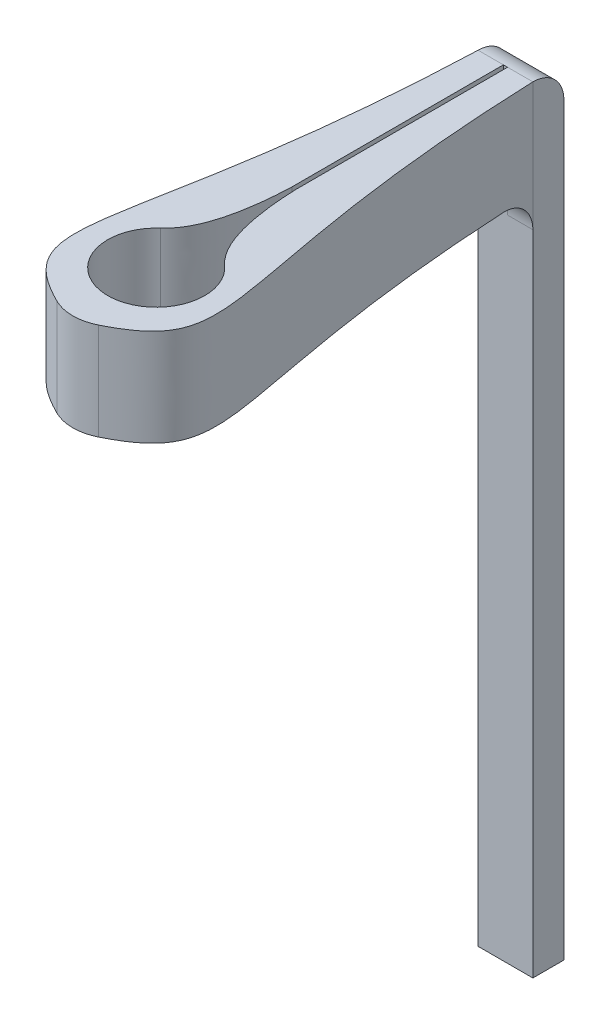
SolidWorks part; units mm, degrees
ref_plane "Front Plane" through (0, 0, 0) normal (0, 0, 1) x (1, 0, 0)
ref_plane "Top Plane" through (0, 0, 0) normal (0, 1, 0) x (1, 0, 0)
ref_plane "Right Plane" through (0, 0, 0) normal (1, 0, 0) x (0, 0, -1)
sketch "Sketch1" plane through (0, 0, 0) normal (0, 1, 0) x (1, 0, 0)
  line L0 (0, 0) -> (0, 6.2146) construction
  line L1 (-1.0541, 2.8957) -> (-0.1615, 3.6883) construction
  line L2 (-0.0683, 13.1387) -> (0.0683, 13.1387)
  line L3 (-0.0683, 13.1387) -> (-0.0683, 6.2146)
  line L5 (0.0683, 13.1387) -> (0.0683, 6.2146)
  line L6 (-0.1615, 3.6883) -> (-0.0683, 6.2146) construction
  line L9 (1.0541, 2.8957) -> (0.1615, 3.6883) construction
  line L10 (0.1615, 3.6883) -> (0.0683, 6.2146) construction
  line L11 (-0.8958, 13.1387) -> (-1.2101, 4.5709) construction
  line L12 (-1.2101, 4.5709) -> (-2.7776, 1.0836) construction
  line L20 (-2.7776, 1.0836) -> (-3.2771, 0.2019) construction
  line L21 (-3.2771, 0.2019) -> (0, -1.17) construction
  line L22 (0.8958, 13.1387) -> (1.2101, 4.5709) construction
  line L23 (1.2101, 4.5709) -> (2.7776, 1.0836) construction
  line L25 (2.7776, 1.0836) -> (3.2771, 0.2019) construction
  line L26 (3.2771, 0.2019) -> (0, -1.17) construction
  line L27 (-0.8958, 13.1387) -> (0, 13.1387)
  line L28 (0.8958, 13.1387) -> (0, 13.1387)
  arc A0 (-1.0541, 2.8957) -> (1.0541, 2.8957) centre (0, 1.7087) ccw
  spline S3 degree 2 poles (1.0541, 2.8957) (0.1615, 3.6883) (0.0683, 6.2146) knots 0 0 0 1 1 1
  spline S4 degree 2 poles (-1.0541, 2.8957) (-0.1615, 3.6883) (-0.0683, 6.2146) knots 0 0 0 1 1 1
  spline S5 degree 4 poles (-0.8958, 13.1387) (-1.2101, 4.5709) (-2.7776, 1.0836) (-3.2771, 0.2019) (0, -1.17) knots 0 0 0 0 0 1 1 1 1 1
  spline S6 degree 4 poles (0.8958, 13.1387) (1.2101, 4.5709) (2.7776, 1.0836) (3.2771, 0.2019) (0, -1.17) knots 0 0 0 0 0 1 1 1 1 1
  point P8 (-0.508, -2.5134)
  point P18 (0.508, -2.5134)
  point P21 (0, -2.54)
  dimension "D6" = 3.6883
  dimension "D1" = 3.175
  dimension "D3" = 0.8958
  dimension "D2" = 11.43
  dimension "D5" = 3.3189
  dimension "D7" = 4.5709
  dimension "D4" = 6.2146
extrude "Boss-Extrude1" add sketch "Sketch1" along normal blind 1.5875 and the other way blind 1.5875 contours S6 L28 L5 S3 A0 S4 L3 L27 S5 region at (0.082, 0, -9.6767)
ref_axis "Axis1" through (0, 0, -2.032) along (0, 0, 1)
ref_plane "Plane1" through (0, 0, 2.54) normal (0, 0, 1) x (1, 0, 0)
ref_axis "Axis2" through (0, 1.7463, 2.54) along (0, -1, 0)
fillet "Fillet1" radius 1.524 1 edges at (0, 0, 1.17)
ref_plane "Plane2" through (0, 0, -2.8957) normal (0, 0, -1) x (-1, 0, 0)
ref_plane "Plane3" through (0, 0, -3.4037) normal (0, 0, -1) x (-1, 0, 0)
sketch "Sketch2" plane through (0, 0, 0) normal (1, 0, 0) x (0, 0, -1)
  line L0 (13.1387, -1.5875) -> (13.1387, 1.5875) construction
  line L1 (13.1387, -1.5875) -> (13.1387, 1.5875)
  line L3 (13.1387, 1.5875) -> (14.1547, 1.5875)
  line L4 (13.1387, 1.5875) -> (13.1387, -23.8125)
  line L5 (13.1387, -23.8125) -> (14.1547, -23.8125)
  line L6 (14.1547, 1.5875) -> (14.1547, -23.8125)
  dimension "D1" = 1.016
  dimension "D2" = 25.4
extrude "Boss-Extrude2" add sketch "Sketch2" along normal up to vertex (0.8958 mm away) and the other way up to vertex (0.8958 mm away) contours L6 L3 L1 L4 L5 region at (0, -11.1125, -13.6467) up to point (0.8958, 1.5875, -13.1387) other way up to point (-0.8958, 1.5875, -13.1387)
fillet "Fillet2" radius 1.016 3 edges at (0, 1.5875, -14.1547)
ref_point "Point1"
